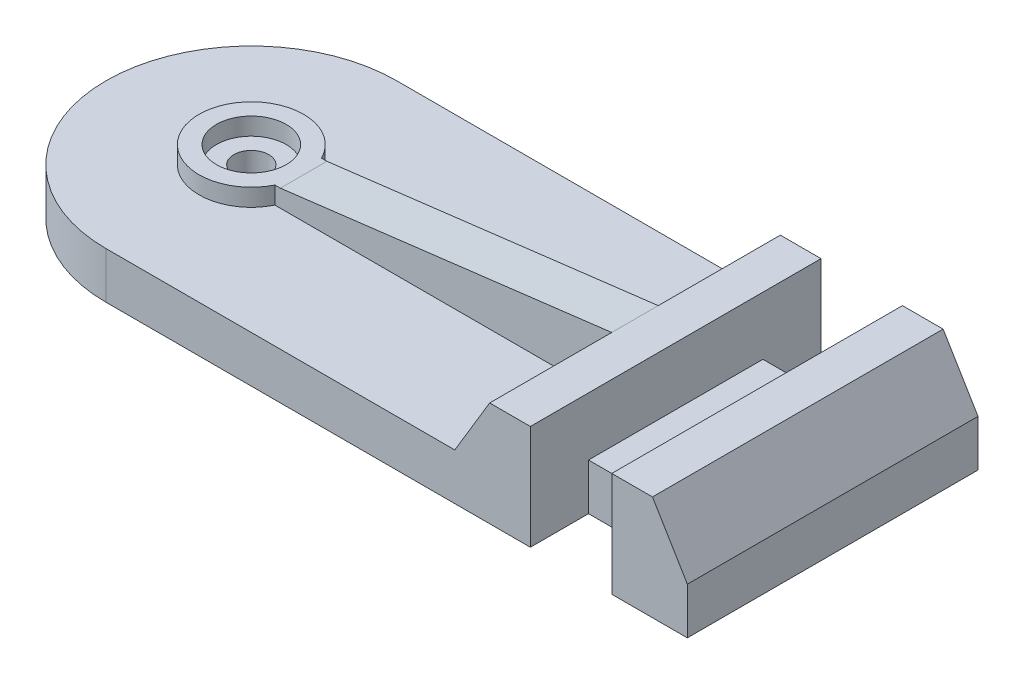
SolidWorks part; units mm, degrees
material "ABS"
ref_plane "前视基准面" through (0, 0, 0) normal (0, 0, 1) x (1, 0, 0)
ref_plane "上视基准面" through (0, 0, 0) normal (0, 1, 0) x (1, 0, 0)
ref_plane "右视基准面" through (0, 0, 0) normal (1, 0, 0) x (0, 0, -1)
sketch "草图1" plane through (0, 0, 0) normal (0, 1, 0) x (1, 0, 0)
  line L0 (0, 12.5) -> (50, 12.5)
  line L1 (50, 12.5) -> (50, -12.5)
  line L2 (50, -12.5) -> (0, -12.5)
  line L3 (-17.9664, 0) -> (77.456, 0) construction
  circle A0 centre (0, 0) radius 12.5
  circle A1 centre (0, 0) radius 1.5
  circle A2 centre (40, 0) radius 1.5
  dimension "D1" = 25
  dimension "D3" = 3
  dimension "D4" = 3
  dimension "D2" = 50
  dimension "D5" = 40
extrude "凸台-拉伸1" add sketch "草图1" along normal blind 4 contours A0 L3 A1 | L3 A0 A1 | A0 L3 A2 L1 L0 | L3 A0 L2 L1 A2 region at (29.7397, 0, -6.5223) region at (0, 0, -5.3734) region at (0, 0, 5.3734) region at (29.7397, 0, 6.5223)
sketch "草图2" plane through (0, 4, 0) normal (0, 1, 0) x (1, 0, 0)
  circle A0 centre (0, 0) radius 3
  circle A1 centre (0, 0) radius 4.5
  dimension "D1" = 6
  dimension "D2" = 9
extrude "凸台-拉伸2" add sketch "草图2" along normal blind 1.5
sketch "草图3" plane through (0, 0, 12.5) normal (0, 0, 1) x (1, 0, 0)
  line L0 (40, 13.5103) -> (40, -9.5748) construction
  line L1 (33, 9) -> (47, 9)
  line L2 (47, 9) -> (50, 4)
  line L3 (50, 4) -> (30, 4)
  line L4 (50, 4) -> (0, 4) construction
  line L5 (33, 9) -> (30, 4)
  point P11 (40, 4)
  point P12 (40, 9)
  dimension "D1" = 40
  dimension "D2" = 7
  dimension "D3" = 5
extrude "凸台-拉伸3" add sketch "草图3" against normal up to surface (25 mm away) up to face at (25, 2, -12.5)
sketch "草图4" plane through (0, 0, 12.5) normal (0, 0, 1) x (1, 0, 0)
  line L0 (40, 14.712) -> (40, -12.897) construction
  line L1 (36.5, 9) -> (43.5, 9)
  line L2 (47, 9) -> (33, 9) construction
  line L3 (43.5, 9) -> (43.5, 4)
  line L4 (43.5, 4) -> (36.5, 4)
  line L5 (36.5, 9) -> (36.5, 4)
  point P10 (40, 4)
  point P11 (40, 9)
  dimension "D1" = 40
  dimension "D2" = 3.5
  dimension "D3" = 5
extrude "切除-拉伸1" cut sketch "草图4" against normal through all
sketch "草图5" plane through (0, 4, 0) normal (0, 1, 0) x (1, 0, 0)
  line L0 (-19.9448, 0) -> (64.5272, 0) construction
  line L1 (36.5, -12.5) -> (43.5, -12.5)
  line L2 (43.5, -12.5) -> (43.5, -7.5)
  line L3 (43.5, 12.5) -> (43.5, -12.5) construction
  line L4 (43.5, -7.5) -> (36.5, -7.5)
  line L5 (36.5, 12.5) -> (36.5, -12.5) construction
  line L6 (36.5, -7.5) -> (36.5, -12.5)
  line L7 (36.5, 7.5) -> (36.5, 12.5)
  line L8 (36.5, 12.5) -> (43.5, 12.5)
  line L9 (43.5, 12.5) -> (43.5, 7.5)
  line L10 (43.5, 7.5) -> (36.5, 7.5)
  dimension "D1" = 5
extrude "切除-拉伸2" cut sketch "草图5" against normal through all
sketch "草图6" plane through (0, 0, 0) normal (0, 0, 1) x (1, 0, 0)
  line L0 (30, 4) -> (33, 9)
  line L1 (33, 9) -> (4.5, 5.5)
  line L2 (4.5, 5.5) -> (-4.5, 5.5) construction
  line L3 (4.5, 4) -> (4.5, 5.5) construction
  line L4 (4.5, 5.5) -> (3.2158, 5.5)
  line L5 (3.2158, 5.5) -> (3.2158, 4)
  line L6 (30, 4) -> (0, 4) construction
  line L7 (3.2158, 4) -> (30, 4)
extrude "凸台-拉伸4" add sketch "草图6" along normal mid plane 4
